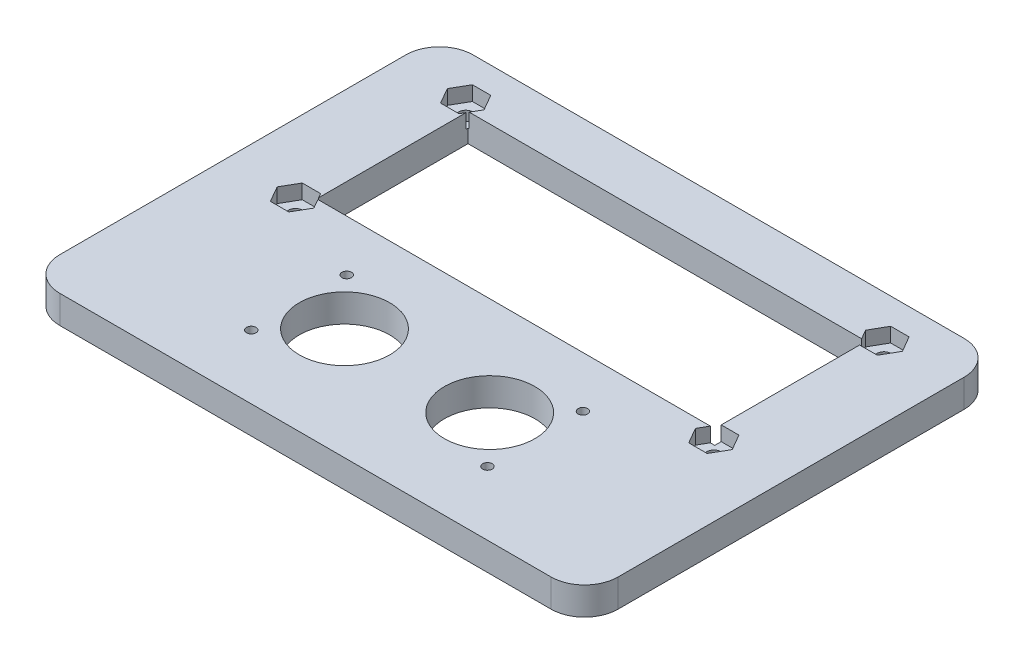
SolidWorks part; units mm, degrees
ref_plane "Front Plane" through (0, 0, 0) normal (0, 0, 1) x (1, 0, 0)
ref_plane "Top Plane" through (0, 0, 0) normal (0, 1, 0) x (1, 0, 0)
ref_plane "Right Plane" through (0, 0, 0) normal (1, 0, 0) x (0, 0, -1)
sketch "Sketch1" plane through (0, 0, 0) normal (0, 1, 0) x (1, 0, 0)
  line L1 (-50, -37) -> (50, -37)
  line L2 (-50, -37) -> (-50, 37)
  line L3 (-50, 37) -> (50, 37)
  line L4 (50, -37) -> (50, 37)
  line L5 (-50, -37) -> (50, 37) construction
  line L6 (-50, 37) -> (50, -37) construction
  point P0 (0, 0)
  dimension "D1" = 100
  dimension "D2" = 74
extrude "Boss-Extrude1" add sketch "Sketch1" along normal blind 5
sketch "Sketch2" plane through (0, 5, 0) normal (0, 1, 0) x (1, 0, 0)
  line L1 (-35.6489, 0.6691) -> (35.6489, 0.6691)
  line L2 (-35.6489, 0.6691) -> (-35.6489, 27.7709)
  line L3 (-35.6489, 27.7709) -> (35.6489, 27.7709)
  line L4 (35.6489, 0.6691) -> (35.6489, 27.7709)
  line L5 (-35.6489, 0.6691) -> (35.6489, 27.7709) construction
  line L6 (-35.6489, 27.7709) -> (35.6489, 0.6691) construction
  line L7 (-40.2971, 14.22) -> (39.7129, 14.22) construction
  line L8 (-40.2971, 32) -> (39.7129, 32) construction
  line L9 (-40.2971, 32) -> (-40.2971, -3.56) construction
  line L10 (-40.2971, -3.56) -> (39.7129, -3.56) construction
  line L11 (39.7129, 32) -> (39.7129, -3.56) construction
  line L12 (50, 37) -> (-50, 37) construction
  circle A0 centre (-37.7571, -1.02) radius 1.27
  circle A1 centre (37.1729, -1.02) radius 1.27
  circle A2 centre (37.1729, 29.46) radius 1.27
  circle A3 centre (-37.7571, 29.46) radius 1.27
  point P0 (0, 14.22)
  point P7 (0, 0)
  point P8 (0, 0)
  point P20 (-0.2921, 14.22)
  dimension "D7" = 2.54
  dimension "D8" = 2.54
  dimension "D1" = 71.2978
  dimension "D2" = 27.1018
  dimension "D3" = 5
  dimension "D4" = 35.56
  dimension "D5" = 80.01
  dimension "D6" = 4.6482
  dimension "D9" = 33.02
  dimension "D10" = 77.47
  dimension "D11" = 5.08
extrude "Screen Cutout" cut sketch "Sketch2" against normal through all
sketch "Sketch8" plane through (0, 5, 0) normal (0, 1, 0) x (1, 0, 0)
  line L1 (-34.4662, 29.458) -> (-36.1099, 32.309)
  line L2 (-36.1099, 32.309) -> (-39.4008, 32.311)
  line L3 (-39.4008, 32.311) -> (-41.048, 29.462)
  line L4 (-41.048, 29.462) -> (-39.4043, 26.611)
  line L5 (-39.4043, 26.611) -> (-36.1134, 26.609)
  line L6 (-36.1134, 26.609) -> (-34.4662, 29.458)
  line L7 (40.4638, 29.4737) -> (38.8065, 32.3168)
  line L8 (38.8065, 32.3168) -> (35.5156, 32.3031)
  line L9 (35.5156, 32.3031) -> (33.882, 29.4463)
  line L10 (33.882, 29.4463) -> (35.5393, 26.6032)
  line L11 (35.5393, 26.6032) -> (38.8302, 26.6169)
  line L12 (38.8302, 26.6169) -> (40.4638, 29.4737)
  line L13 (40.4638, -1.0191) -> (38.8176, 1.8304)
  line L14 (38.8176, 1.8304) -> (35.5267, 1.8296)
  line L15 (35.5267, 1.8296) -> (33.882, -1.0209)
  line L16 (33.882, -1.0209) -> (35.5282, -3.8704)
  line L17 (35.5282, -3.8704) -> (38.8191, -3.8696)
  line L18 (38.8191, -3.8696) -> (40.4638, -1.0191)
  line L19 (-41.048, -1.02) -> (-39.4025, -3.87)
  line L20 (-39.4025, -3.87) -> (-36.1117, -3.87)
  line L21 (-36.1117, -3.87) -> (-34.4662, -1.02)
  line L22 (-34.4662, -1.02) -> (-36.1117, 1.83)
  line L23 (-36.1117, 1.83) -> (-39.4025, 1.83)
  line L24 (-39.4025, 1.83) -> (-41.048, -1.02)
  circle A0 centre (-37.7571, 29.46) radius 2.85 construction
  circle A1 centre (37.1729, 29.46) radius 2.85 construction
  circle A2 centre (37.1729, -1.02) radius 2.85 construction
  circle A3 centre (-37.7571, -1.02) radius 2.85 construction
  dimension "D1" = 5.7
extrude "Screen hex nuts" cut sketch "Sketch8" against normal blind 2.6
sketch "Sketch3" plane through (0, 5, 0) normal (0, 1, 0) x (1, 0, 0)
  line L0 (-13, -17) -> (13, -17) construction
  line L1 (-21.15, -8.45) -> (-21.15, -25.55) construction
  line L2 (-21.15, -25.55) -> (21.15, -25.55) construction
  line L3 (0, -19.6293) -> (0, -12.0788) construction
  line L4 (-50, -37) -> (50, -37) construction
  circle A0 centre (-13, -17) radius 8.1
  circle A1 centre (13, -17) radius 8.1
  circle A2 centre (-21.15, -8.45) radius 0.85
  circle A3 centre (21.15, -8.45) radius 0.85
  circle A4 centre (21.15, -25.55) radius 0.85
  circle A5 centre (-21.15, -25.55) radius 0.85
  point P4 (-21.15, -17)
  point P17 (0, -25.55)
  point P20 (0, 0)
  dimension "D1" = 16.2
  dimension "D2" = 26
  dimension "D3" = 1.7
  dimension "D4" = 17.1
  dimension "D5" = 20
  dimension "D6" = 42.3
extrude "Ultrasound Cutouts" cut sketch "Sketch3" against normal through all
sketch "Sketch4" plane through (0, 5, 0) normal (0, 1, 0) x (1, 0, 0)
  circle A0 centre (-21.6513, -28.8183) radius 0.85
  circle A1 centre (20.3487, -11.8183) radius 0.85
  circle A2 centre (-21.6513, -11.8183) radius 0.85
  circle A3 centre (20.3487, -28.8183) radius 0.85
  dimension "D1" = 1.7
  dimension "D2" = 17
  dimension "D3" = 42
extrude "Ultrasound Bolt Holes" [suppressed] cut sketch "Sketch4" against normal through all
sketch "Sketch5" plane through (0, 0, 0) normal (0, -1, 0) x (1, 0, 0)
  line L0 (21.0023, 26.3871) -> (-21.0023, 26.3871) construction
  line L1 (5.8503, 26.3871) -> (-6.1497, 26.3871)
  line L2 (5.8503, 26.3871) -> (5.8503, 22.3871)
  line L3 (5.8503, 22.3871) -> (-6.1497, 22.3871)
  line L4 (-6.1497, 26.3871) -> (-6.1497, 22.3871)
  line L5 (5.8503, 26.3871) -> (-6.1497, 22.3871) construction
  line L6 (5.8503, 22.3871) -> (-6.1497, 26.3871) construction
  circle A3 centre (21.15, 25.55) radius 0.85 construction
  circle A4 centre (-21.15, 25.55) radius 0.85 construction
  point P0 (-0.1497, 24.3871)
  dimension "D1" = 12
  dimension "D2" = 4
extrude "US Clock cutout" cut sketch "Sketch5" against normal blind 4
sketch "Sketch6" plane through (0, 0, 0) normal (0, -1, 0) x (1, 0, 0)
  line L0 (5.8503, 24.3871) -> (-6.1497, 24.3871) construction
  line L1 (5, 10.1371) -> (-5, 10.1371)
  line L2 (5, 10.1371) -> (5, 6.6371)
  line L3 (5, 6.6371) -> (-5, 6.6371)
  line L4 (-5, 10.1371) -> (-5, 6.6371)
  line L5 (5, 10.1371) -> (-5, 6.6371) construction
  line L6 (5, 6.6371) -> (-5, 10.1371) construction
  line L7 (5.8503, 22.3871) -> (5.8503, 26.3871) construction
  line L8 (-6.1497, 26.3871) -> (-6.1497, 22.3871) construction
  line L9 (21.9766, 8.648) -> (-21.9766, 8.648) construction
  line L10 (0, 5.8213) -> (0, 1.0358) construction
  circle A0 centre (21.15, 8.45) radius 0.85 construction
  circle A1 centre (-21.15, 8.45) radius 0.85 construction
  point P0 (0, 8.3871)
  dimension "D1" = 10
  dimension "D2" = 3.5
  dimension "D3" = 16
extrude "US Pin cutout" cut sketch "Sketch6" against normal blind 2
ref_plane "Magnet plane" through (0, 0.2, 0) normal (0, -1, 0) x (-1, 0, 0)
sketch "Sketch9" plane through (0, 0.2, 0) normal (0, -1, 0) x (-1, 0, 0)
  line L0 (-50, -37) -> (-50, 37) construction
  line L1 (-50, 37) -> (50, 37) construction
  line L2 (50, -37) -> (-50, -37) construction
  line L3 (50, 37) -> (50, -37) construction
  circle A0 centre (-44, 31) radius 3.15
  circle A1 centre (44, 31) radius 3.15
  circle A2 centre (-44, -31) radius 3.15
  circle A3 centre (44, -31) radius 3.15
  point P8 (0, 0)
  point P9 (0, 0)
  point P10 (0, 0)
  point P11 (0, 0)
  dimension "D1" = 6.3
  dimension "D2" = 6
  dimension "D3" = 6
  dimension "D4" = 6
  dimension "D5" = 6
extrude "Magnet Holes" cut sketch "Sketch9" against normal blind 2.1
fillet "Fillet1" radius 6 4 edges at (50, 2.5, -37) (50, 2.5, 37) (-50, 2.5, 37) (-50, 2.5, -37)
fillet "Fillet2" radius 1 4 edges at (5.8503, 2, 26.3871) (-6.1497, 2, 26.3871) (-6.1497, 2, 22.3871) (5.8503, 2, 22.3871)
